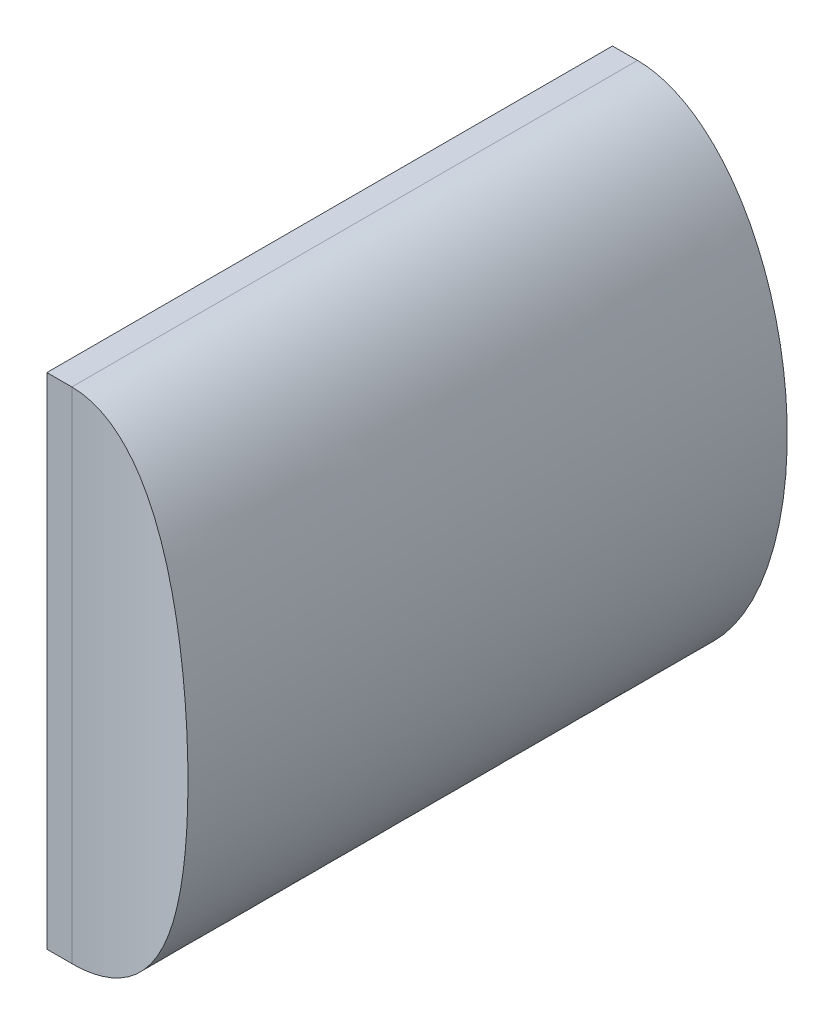
SolidWorks part; units mm, degrees
ref_plane "Front Plane" through (0, 0, 0) normal (0, 0, 1) x (1, 0, 0)
ref_plane "Top Plane" through (0, 0, 0) normal (0, 1, 0) x (1, 0, 0)
ref_plane "Right Plane" through (0, 0, 0) normal (1, 0, 0) x (0, 0, -1)
sketch "Sketch1" plane through (0, 0, 0) normal (0, 0, 1) x (1, 0, 0)
  line L0 (0, 0) -> (30, 0) construction
  line L1 (0, 50) -> (0, -50) construction
  line L3 (0, 50) -> (0, -50)
  ellipse E0 centre (0, 0) end of major axis (0, -50) minor radius 30 (0, -50) -> (0, 50) ccw
  point P2 (0, 0)
  dimension "D1" = 30
  dimension "D2" = 100
extrude "Boss-Extrude4" add sketch "Sketch1" along normal mid plane 120 contours L3 E0
sketch "Sketch2" plane through (0, 0, 0) normal (0, 1, 0) x (1, 0, 0)
  line L0 (0, 95.4885) -> (0, -95.4885) construction
  line L1 (30, -60) -> (0, -60)
  line L2 (0, -60) -> (0, -53.2456)
  arc A0 (30, -60) -> (0, -53.2456) centre (0, -123.2456) ccw
  point P3 (0, 0)
  dimension "D1" = 70
extrude "Cut-Extrude2" cut sketch "Sketch2" against normal through all both and the other way through all contours L1 L2 A0
shell "Shell3" thickness 4 removed face at (0, -12.5, 24.9342)
sketch "Sketch3" plane through (0, 0, 0) normal (-1, 0, 0) x (0, 0, 1)
  line L0 (49.2456, -46) -> (-56, -46) construction
  line L1 (-56, 46) -> (-56, -46) construction
  line L2 (49.2456, 46) -> (-56, 46) construction
  line L3 (49.2456, -46) -> (49.2456, 46) construction
  line L4 (-60, -50) -> (53.2456, -50)
  line L5 (53.2456, -50) -> (53.2456, 50)
  line L6 (53.2456, 50) -> (-60, 50)
  line L7 (-60, 50) -> (-60, -50)
  line L8 (-60, -50) -> (53.2456, -50)
  line L9 (53.2456, -50) -> (53.2456, 50)
  line L10 (53.2456, 50) -> (-60, 50)
  line L11 (-60, 50) -> (-60, -50)
  line L12 (49.2456, -46) -> (-56, -46)
  line L13 (-56, 46) -> (-56, -46)
  line L14 (49.2456, 46) -> (-56, 46)
  line L15 (49.2456, -46) -> (49.2456, 46)
  line L16 (51.9122, 48.6667) -> (-58.6667, 48.6667)
  line L17 (-58.6667, 48.6667) -> (-58.6667, -48.6667)
  line L18 (-58.6667, -48.6667) -> (51.9122, -48.6667)
  line L19 (51.9122, -48.6667) -> (51.9122, 48.6667)
  line L20 (50.5789, 47.3333) -> (-57.3333, 47.3333)
  line L21 (-57.3333, 47.3333) -> (-57.3333, -47.3333)
  line L22 (50.5789, -47.3333) -> (-57.3333, -47.3333)
  line L23 (50.5789, -47.3333) -> (50.5789, 47.3333)
  line M6 (49.2456, 46) -> (49.2456, -46)
  line M7 (49.2456, -46) -> (-56, -46)
  line M8 (-56, -46) -> (-56, 46)
  line M9 (-56, 46) -> (49.2456, 46)
  line M10 (-60, -50) -> (53.2456, -50)
  line M11 (53.2456, -50) -> (53.2456, 50)
  line M12 (53.2456, 50) -> (-60, 50)
  line M13 (-60, 50) -> (-60, -50)
  dimension "D1" = 0
  dimension "D2" = 1.3333
  dimension "D3" = 1.3333
extrude "Boss-Extrude5" add sketch "Sketch3" along normal blind 5 contours L19 L18 L17 L16 M13 M10 M11 M12 | L22 L23 L20 L21 M9 M6 M7 M8 region at (0, 0, -59.8489) region at (0, 0, 50.4353)
